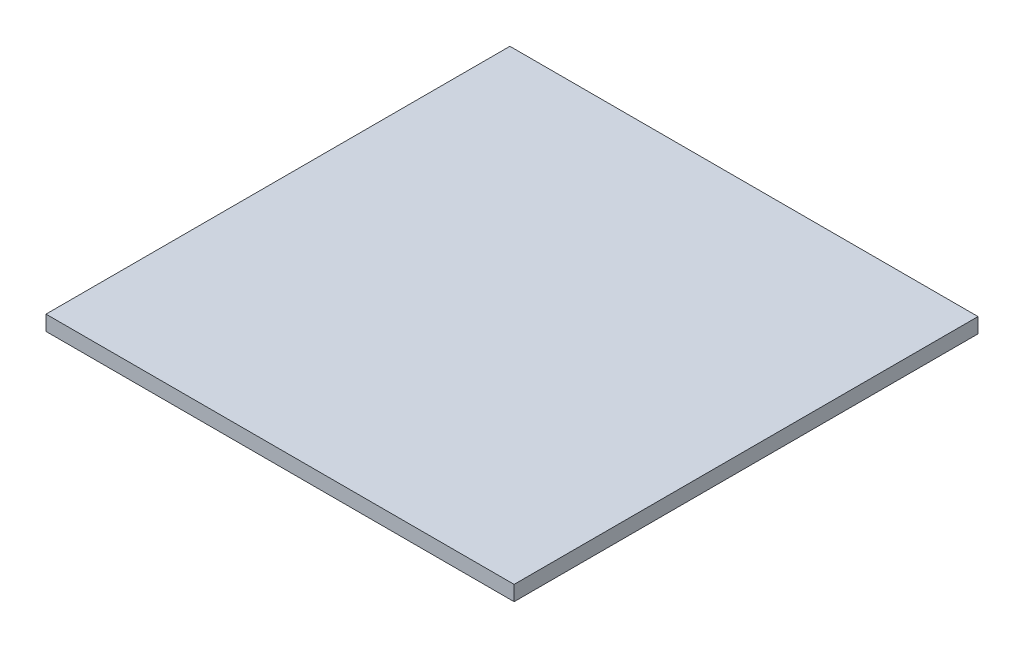
SolidWorks part; units mm, degrees
ref_plane "Front Plane" through (0, 0, 0) normal (0, 0, 1) x (1, 0, 0)
ref_plane "Top Plane" through (0, 0, 0) normal (0, 1, 0) x (1, 0, 0)
ref_plane "Right Plane" through (0, 0, 0) normal (1, 0, 0) x (0, 0, -1)
sketch "Sketch1" plane through (0, 0, 0) normal (0, 1, 0) x (1, 0, 0)
  line L1 (-44.2815, 20.698) -> (55.4185, 20.698)
  line L2 (-44.2815, 20.698) -> (-44.2815, -78.102)
  line L3 (-44.2815, -78.102) -> (55.4185, -78.102)
  line L4 (55.4185, 20.698) -> (55.4185, -78.102)
  dimension "D1" = 99.7
  dimension "D2" = 98.8
extrude "Boss-Extrude1" add sketch "Sketch1" along normal blind 3.2
equation "\"Fit\"= 1"
equation "\"cover width\"= 98.8"
equation "\"bottom 3 length\"= 99.7"
equation "\"thinner acrylic\"= 3.2"
equation "\"D1@Sketch1\"=\"bottom 3 length\""
equation "\"D2@Sketch1\"=\"cover width\""
equation "\"D1@Boss-Extrude1\"=\"thinner acrylic\""
